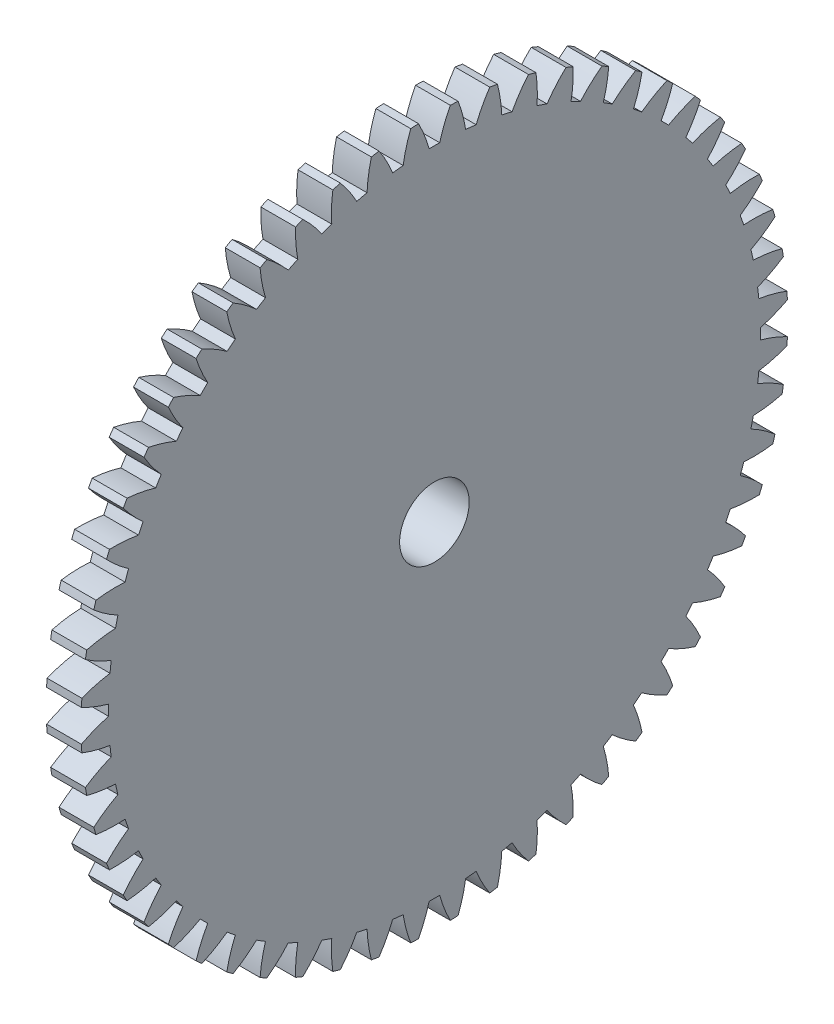
SolidWorks part; units mm, degrees
note: The reader was unsure of these and kept them because the rebuilt part matched: shared geometry of "Sketch1<2>".
ref_plane "Plane1" through (0, 0, 0) normal (0, 0, 1) x (1, 0, 0)
ref_plane "Plane2" through (0, 0, 0) normal (0, 1, 0) x (1, 0, 0)
ref_plane "Plane3" through (0, 0, 0) normal (1, 0, 0) x (0, 0, -1)
sketch "HoldingSke" plane through (0, 0, 0) normal (0, 1, 0) x (1, 0, 0)
  line L0 (0, 0) -> (0.7988, -1.1843)
  line L1 (-15, 0) -> (100, 0) construction
  line L2 (0, 0) -> (-2.1039, 2.3779)
  line L3 (0, 0) -> (-11.863, 4.5341)
  line L4 (0, 0) -> (4.8292, 7.1596)
  line L5 (0, 0) -> (-9.3695, -3.4946)
  line L6 (0, 0) -> (-1.6579, -1.1186)
  line L7 (-2.1039, 2.3779) -> (0.0486, 12.1435)
  line L8 (-76.2, 54.61) -> (-75.5, 54.61)
  line L9 (-71.009, 38.7566) -> (-53.1078, 45.2721)
  line L10 (-76.2, 71.12) -> (104.1128, 71.12)
  line L11 (0, 0) -> (-2, 0)
  line L12 (-76.2, 101.6) -> (-76.173, 101.6)
  line L13 (24.9733, 27.94) -> (52.9518, 28.4284)
  line L14 (24.9733, 27.94) -> (24.9743, 27.94)
  line L15 (24.9733, 27.94) -> (100.4006, 29.5858)
  line L16 (-63.627, -0.7) -> (-12.827, -0.7)
  circle A0 centre (0, 0) radius 2
  circle A1 centre (0, 0) radius 4.5
  circle A2 centre (0, 0) radius 4.5
  circle A3 centre (0, 0) radius 2
  dimension "MHD" = 9
  dimension "Hub_dia" = 9
  dimension "Bore" = 4
  dimension "MBD" = 4
  dimension "Num_teeth" = 56
  dimension "Pitch_radius" = 180.3128
  dimension "Pitch" = 1.4286
  dimension "Width" = 2
  dimension "Overall_len" = 10
  dimension "Show_teeth" = 56
  dimension "Thickness" = 2
  dimension "OAL" = 10.0001
  dimension "T_dim" = 0.7
  dimension "Ap" = 20
  dimension "H" = 19.05
  dimension "Backlash" = 0.027
  dimension "Addendum_fac" = 1
  dimension "Dedendum_fac" = 1.25
  dimension "Clearance_fac" = 0.25
  dimension "Dedendum_add" = 0.001
  dimension "Module" = 0.7
sketch "BasProSke" plane through (0, 0, 0) normal (0, 1, 0) x (1, 0, 0)
  line L0 (-10, 0) -> (60, 0) construction
  line L1 (0, 0) -> (0, 20.3)
  line L2 (0, 0) -> (2, 0)
  line L3 (2, 0) -> (2, 20.3)
  line L4 (2, 20.3) -> (0, 20.3)
  dimension "Diameter" = 40.6
  dimension "Thickness" = 2
revolve "Base-Revolve" add sketch "BasProSke" angle 360 about L0
sketch "TooCutSke" plane through (0, 0, 0) normal (1, 0, 0) x (0, 0, -1)
  line L1 (0, 0) -> (0, 107) construction
  line L2 (0, 0) -> (-0.597, 19.5909) construction
  line L3 (0, 0) -> (-2.1972, 39.1255) construction
  line L4 (-0.597, 19.5909) -> (-1.0986, 19.5627) construction
  arc A0 (0.3036, 18.7215) -> (-0.3036, 18.7215) centre (0, 0) ccw
  arc A1 (0.9277, 20.3042) -> (-0.9277, 20.3042) centre (0, 0) ccw
  circle A2 centre (0, 0) radius 19.6 construction
  circle A3 centre (0, 0) radius 18.418 construction
  arc A4 (-0.3036, 18.7215) -> (-0.9277, 20.3042) centre (-7.866, 16.6538) ccw
  arc A5 (0.9277, 20.3042) -> (0.3036, 18.7215) centre (7.866, 16.6538) ccw
  dimension "Root_dia" = 37.448
  dimension "Overcut_dia" = 40.6508
  dimension "Pitch_dia" = 39.2
  dimension "Base_dia" = 36.836
  dimension "Flank_rad" = 7.84
  dimension "Half_ang" = 3.214
  dimension "Half_CT" = 0.5025
extrude "ToothCut" cut sketch "TooCutSke" along normal through all
fillet "Breaks" [suppressed] radius 0.014
fillet "RootFillets" [suppressed] radius 0.176
pattern_circular "TeethCuts" count 56 every 6.429 about axis through (-10, 0, 0) along (1, 0, 0) of "ToothCut", "RootFillets", "Breaks"
sketch "HubNeaOneSke" plane through (0, 0, 0) normal (-1, 0, 0) x (0, 0, 1)
  circle A0 centre (0, 0) radius 4.5
  dimension "Diameter" = 9
extrude "HubNearOne" add sketch "HubNeaOneSke" along normal blind 8.0001
sketch "HubNeaBotSke" plane through (0, 0, 0) normal (-1, 0, 0) x (0, 0, 1)
  circle A0 centre (0, 0) radius 4.5
  dimension "Diameter" = 9
extrude "HubNearBoth" [suppressed] add sketch "HubNeaBotSke" along normal blind 4
ref_plane "FarPln" through (2, 0, 0) normal (1, 0, 0) x (0, 0, -1)
sketch "HubFarSke" plane through (2, 0, 0) normal (1, 0, 0) x (0, 0, -1)
  circle A0 centre (0, 0) radius 4.5
  dimension "Diameter" = 9
extrude "HubFar" [suppressed] add sketch "HubFarSke" along normal blind 4
sketch "BorSke" plane through (0, 0, 0) normal (1, 0, 0) x (0, 0, -1)
  circle A0 centre (0, 0) radius 2
  dimension "Diameter" = 4
extrude "Bore" cut sketch "BorSke" along normal mid plane 20.0001
sketch "KeySke" plane through (0, 0, 0) normal (1, 0, 0) x (0, 0, -1)
  line L0 (-0.8, 0) -> (-0.8, 2.7)
  line L1 (-0.8, 2.7) -> (0.8, 2.7)
  line L2 (0.8, 2.7) -> (0.8, 0)
  line L3 (0, 0) -> (0, 34) construction
  line L4 (-0.8, 0) -> (0.8, 0)
  dimension "Offset" = 2.7
  dimension "Width" = 1.6
extrude "Keyway" [suppressed] cut sketch "KeySke" along normal mid plane 20.0001
pattern_circular "Keyway2" [suppressed] count 2 every 90 about axis through (-10, 0, 0) along (1, 0, 0)
sketch "Sketch1" plane through (0, 0, 0) normal (0, 0, 1) x (1, 0, 0)
  line L0 (0, 0.3036) -> (0, -0.3036) construction
  circle A0 centre (-4, 0) radius 1.25
  dimension "D1" = 4
curve "Helix/Spiral1" pitch 0.5 height 5 turns 10
extrude "Cut-Extrude1" cut sketch "Sketch1<2>" against normal blind 5
sketch "Sketch1<2>" plane through (0, 0, 0) normal (0, 0, 1) x (1, 0, 0) same geometry as "Sketch1"
sketch "Sketch2" plane through (0, 0, 0) normal (0, 1, 0) x (1, 0, 0)
  line L0 (-5.2214, 3.017) -> (-5.2214, 5.5752) construction
  line L2 (-5.2214, 5.0799) -> (-5.2214, 5.3685)
  line L3 (-5.2214, 5.3685) -> (-5.3964, 5.2675)
  line L4 (-5.3964, 5.1809) -> (-5.2214, 5.0799)
  circle A0 centre (-5.3047, 5.2242) radius 0.0833 construction
  arc A1 (-5.3964, 5.2675) -> (-5.3964, 5.1809) centre (-5.3714, 5.2242) ccw
  spline S0 degree 3 poles (-5.25, 0) (-5.25, 0.0104) (-5.1849, 0.0313) (-4.9069, 0.0625) (-4.4908, 0.0938) (-4, 0.125) (-3.5092, 0.1563) (-3.0931, 0.1875) (-2.8151, 0.2188) (-2.7175, 0.25) (-2.8151, 0.2813) (-3.0931, 0.3125) (-3.5092, 0.3438) (-4, 0.375) (-4.4908, 0.4063) (-4.9069, 0.4375) (-5.1849, 0.4688) (-5.2825, 0.5) (-5.1849, 0.5313) (-4.9069, 0.5625) (-4.4908, 0.5938) (-4, 0.625) (-3.5092, 0.6563) (-3.0931, 0.6875) (-2.8151, 0.7188) (-2.7175, 0.75) (-2.8151, 0.7813) (-3.0931, 0.8125) (-3.5092, 0.8438) (-4, 0.875) (-4.4908, 0.9063) (-4.9069, 0.9375) (-5.1849, 0.9688) (-5.2825, 1) (-5.1849, 1.0313) (-4.9069, 1.0625) (-4.4908, 1.0938) (-4, 1.125) (-3.5092, 1.1563) (-3.0931, 1.1875) (-2.8151, 1.2188) (-2.7175, 1.25) (-2.8151, 1.2813) (-3.0931, 1.3125) (-3.5092, 1.3438) (-4, 1.375) (-4.4908, 1.4063) (-4.9069, 1.4375) (-5.1849, 1.4688) (-5.2825, 1.5) (-5.1849, 1.5313) (-4.9069, 1.5625) (-4.4908, 1.5938) (-4, 1.625) (-3.5092, 1.6563) (-3.0931, 1.6875) (-2.8151, 1.7188) (-2.7175, 1.75) (-2.8151, 1.7813) (-3.0931, 1.8125) (-3.5092, 1.8438) (-4, 1.875) (-4.4908, 1.9063) (-4.9069, 1.9375) (-5.1849, 1.9688) (-5.2825, 2) (-5.1849, 2.0313) (-4.9069, 2.0625) (-4.4908, 2.0938) (-4, 2.125) (-3.5092, 2.1563) (-3.0931, 2.1875) (-2.8151, 2.2188) (-2.7175, 2.25) (-2.8151, 2.2813) (-3.0931, 2.3125) (-3.5092, 2.3438) (-4, 2.375) (-4.4908, 2.4063) (-4.9069, 2.4375) (-5.1849, 2.4688) (-5.2825, 2.5) (-5.1849, 2.5313) (-4.9069, 2.5625) (-4.4908, 2.5938) (-4, 2.625) (-3.5092, 2.6563) (-3.0931, 2.6875) (-2.8151, 2.7188) (-2.7175, 2.75) (-2.8151, 2.7813) (-3.0931, 2.8125) (-3.5092, 2.8438) (-4, 2.875) (-4.4908, 2.9063) (-4.9069, 2.9375) (-5.1849, 2.9688) (-5.2825, 3) (-5.1849, 3.0313) (-4.9069, 3.0625) (-4.4908, 3.0938) (-4, 3.125) (-3.5092, 3.1563) (-3.0931, 3.1875) (-2.8151, 3.2188) (-2.7175, 3.25) (-2.8151, 3.2813) (-3.0931, 3.3125) (-3.5092, 3.3438) (-4, 3.375) (-4.4908, 3.4063) (-4.9069, 3.4375) (-5.1849, 3.4688) (-5.2825, 3.5) (-5.1849, 3.5313) (-4.9069, 3.5625) (-4.4908, 3.5938) (-4, 3.625) (-3.5092, 3.6563) (-3.0931, 3.6875) (-2.8151, 3.7188) (-2.7175, 3.75) (-2.8151, 3.7813) (-3.0931, 3.8125) (-3.5092, 3.8438) (-4, 3.875) (-4.4908, 3.9063) (-4.9069, 3.9375) (-5.1849, 3.9688) (-5.2825, 4) (-5.1849, 4.0313) (-4.9069, 4.0625) (-4.4908, 4.0938) (-4, 4.125) (-3.5092, 4.1563) (-3.0931, 4.1875) (-2.8151, 4.2188) (-2.7175, 4.25) (-2.8151, 4.2813) (-3.0931, 4.3125) (-3.5092, 4.3438) (-4, 4.375) (-4.4908, 4.4063) (-4.9069, 4.4375) (-5.1849, 4.4687) (-5.2825, 4.5) (-5.1849, 4.5312) (-4.9069, 4.5625) (-4.4908, 4.5937) (-4, 4.625) (-3.5092, 4.6562) (-3.0931, 4.6875) (-2.8151, 4.7187) (-2.7175, 4.75) (-2.8151, 4.7812) (-3.0931, 4.8125) (-3.5092, 4.8437) (-4, 4.875) (-4.4908, 4.9062) (-4.9069, 4.9375) (-5.1849, 4.9687) (-5.25, 4.9896) (-5.25, 5) knots 0 0 0 0 0.00625 0.0125 0.01875 0.025 0.03125 0.0375 0.04375 0.05 0.05625 0.0625 0.06875 0.075 0.08125 0.0875 0.09375 0.1 0.10625 0.1125 0.11875 0.125 0.13125 0.1375 0.14375 0.15 0.15625 0.1625 0.16875 0.175 0.18125 0.1875 0.19375 0.2 0.20625 0.2125 0.21875 0.225 0.23125 0.2375 0.24375 0.25 0.25625 0.2625 0.26875 0.275 0.28125 0.2875 0.29375 0.3 0.30625 0.3125 0.31875 0.325 0.33125 0.3375 0.34375 0.35 0.35625 0.3625 0.36875 0.375 0.38125 0.3875 0.39375 0.4 0.40625 0.4125 0.41875 0.425 0.43125 0.4375 0.44375 0.45 0.45625 0.4625 0.46875 0.475 0.48125 0.4875 0.49375 0.5 0.50625 0.5125 0.51875 0.525 0.53125 0.5375 0.54375 0.55 0.55625 0.5625 0.56875 0.575 0.58125 0.5875 0.59375 0.6 0.60625 0.6125 0.61875 0.625 0.63125 0.6375 0.64375 0.65 0.65625 0.6625 0.66875 0.675 0.68125 0.6875 0.69375 0.7 0.70625 0.7125 0.71875 0.725 0.73125 0.7375 0.74375 0.75 0.75625 0.7625 0.76875 0.775 0.78125 0.7875 0.79375 0.8 0.80625 0.8125 0.81875 0.825 0.83125 0.8375 0.84375 0.85 0.85625 0.8625 0.86875 0.875 0.88125 0.8875 0.89375 0.9 0.90625 0.9125 0.91875 0.925 0.93125 0.9375 0.94375 0.95 0.95625 0.9625 0.96875 0.975 0.98125 0.9875 0.99375 1 1 1 1 construction
  point P11 (-5.4714, 5.2242)
  dimension "D2" = 0.05
  dimension "D1" = 0.25
sweep "Cut-Sweep1" cut profiles "Sketch2" path "Helix/Spiral1"
ref_plane "Plane4" through (0, 0, -4.5) normal (0, 0, 1) x (1, 0, 0)
sketch "Sketch3" plane through (0, 0, -4.5) normal (0, 0, 1) x (1, 0, 0)
  circle A0 centre (-4, 0) radius 1.55
extrude "Cut-Extrude2" cut sketch "Sketch3" along normal blind 5 draft 45
equation "' \"Module@HoldingSke\" = 6.35"
equation "' \"Num_teeth@HoldingSke\" = 12"
equation "' \"Ap@HoldingSke\" =  20"
equation "' \"Width@HoldingSke\" = 0.5 * 25.4"
equation "' \"Hub_dia@HoldingSke\"= 1 * 25.4"
equation "' \"Overall_len@HoldingSke\" = 1.0 * 25.4"
equation "' \"Bore@HoldingSke\" = 0.75 * 25.4"
equation "' \"T_dim@HoldingSke\" = 0.1 * 25.4"
equation "' \"Width@KeySke\" = 0.25 * 25.4"
equation "' \"Show_teeth@HoldingSke\" = 13"
equation "' \"Backlash@HoldingSke\" = 0.009 * 25.4"
equation "' \"Addendum_fac@HoldingSke\" = 1.0"
equation "' \"Dedendum_fac@HoldingSke\" = 1.25"
equation "' \"Dedendum_add@HoldingSke\" = 0.00005 * 25.4"
equation "' \"Clearance_fac@HoldingSke\" = 0.25"
equation "\"Pitch@HoldingSke\" = 1 / \"Module@HoldingSke\""
equation "\"Overcut_dia@TooCutSke\" = (\"Num_teeth@HoldingSke\" + 2 * \"Addendum_fac@HoldingSke\") / \"Pitch@HoldingSke\" + 0.002 * 25.4"
equation "\"Pitch_dia@TooCutSke\" = \"Num_teeth@HoldingSke\" / \"Pitch@HoldingSke\""
equation "\"Base_dia@TooCutSke\" = \"Num_teeth@HoldingSke\" / \"Pitch@HoldingSke\" * cos((\"Ap@HoldingSke\"  * 3.14159265 / 180))"
equation "\"Root_dia@TooCutSke\" = (\"Num_teeth@HoldingSke\" + 2) / \"Pitch@HoldingSke\" - 2 * (\"Addendum_fac@HoldingSke\" + \"Dedendum_fac@HoldingSke\") / \"Pitch@HoldingSke\" - \"Dedendum_add@HoldingSke\" * 2"
equation "\"Half_ang@TooCutSke\" = 180 / \"Num_teeth@HoldingSke\""
equation "\"Half_CT@TooCutSke\" = \"Num_teeth@HoldingSke\" / \"Pitch@HoldingSke\" * sin((3.14159265 / 2 / \"Num_teeth@HoldingSke\")) / 2 - 7 * \"Backlash@HoldingSke\" / 4"
equation "\"Flank_rad@TooCutSke\" = \"Num_teeth@HoldingSke\" / \"Pitch@HoldingSke\" / 5"
equation "\"Radius@RootFillets\" = \"Clearance_fac@HoldingSke\" / \"Pitch@HoldingSke\" + \"Dedendum_add@HoldingSke\""
equation "\"Break_rad@Breaks\" = 0.02 / \"Pitch@HoldingSke\""
equation "\"Thickness@HoldingSke\" = \"Width@HoldingSke\""
equation "\"OAL@HoldingSke\" = \"Thickness@HoldingSke\""
equation "\"MHD@HoldingSke\" = (\"Num_teeth@HoldingSke\" + 2) / \"Pitch@HoldingSke\" - 2 * (\"Addendum_fac@HoldingSke\" + \"Dedendum_fac@HoldingSke\")  / \"Pitch@HoldingSke\" - \"Dedendum_add@HoldingSke\" * 2"
equation "\"MBD@HoldingSke\" = (\"Num_teeth@HoldingSke\" + 2) / \"Pitch@HoldingSke\" - 2 * (\"Addendum_fac@HoldingSke\" + \"Dedendum_fac@HoldingSke\")  / \"Pitch@HoldingSke\" - \"Dedendum_add@HoldingSke\" * 2 - 0.002 * 25.4"
equation "\"MHD@HoldingSke\" = ((sgn( \"MHD@HoldingSke\" - \"Hub_dia@HoldingSke\" )-1)*( \"MHD@HoldingSke\" - \"Hub_dia@HoldingSke\" ))/-2+ \"Hub_dia@HoldingSke\""
equation "\"MBD@HoldingSke\" = ((sgn( \"MBD@HoldingSke\" - \"Bore@HoldingSke\" )-1)*( \"MBD@HoldingSke\" - \"Bore@HoldingSke\" ))/-2+ \"Bore@HoldingSke\""
equation "\"OAL@HoldingSke\" = ((sgn( \"OAL@HoldingSke\" - \"Overall_len@HoldingSke\" )+1)*( \"OAL@HoldingSke\" - \"Overall_len@HoldingSke\" ))/2 + \"Overall_len@HoldingSke\" + 0.000002 * 25.4"
equation "\"Num_teeth@TeethCuts\" = int( \"Show_teeth@HoldingSke\" ) + 1"
equation "\"Num_teeth@TeethCuts\" = ((sgn( \"Num_teeth@TeethCuts\" - \"Num_teeth@HoldingSke\" )-1)*( \"Num_teeth@TeethCuts\" - \"Num_teeth@HoldingSke\" ))/-2+ \"Num_teeth@HoldingSke\""
equation "\"Num_teeth@TeethCuts\" = ((sgn( \"Num_teeth@TeethCuts\" - 2.0)+1)*( \"Num_teeth@TeethCuts\" - 2.0))/2 +2.0"
equation "\"Angle@TeethCuts\" = 360.0 / \"Num_teeth@HoldingSke\""
equation "\"Diameter@BasProSke\" = (\"Num_teeth@HoldingSke\" + 2 * \"Addendum_fac@HoldingSke\") / \"Pitch@HoldingSke\""
equation "\"Thickness@BasProSke\"  = \"Thickness@HoldingSke\""
equation "' \"Fillet_rad@BasProSke\" =  \"Thickness@HoldingSke\" * 0.05"
equation "\"MHD@HoldingSke\" = ((sgn( \"MHD@HoldingSke\" - \"Root_dia@TooCutSke\" )-1)*( \"MHD@HoldingSke\" - \"Root_dia@TooCutSke\" ))/-2+ \"Root_dia@TooCutSke\""
equation "\"Diameter@HubNeaOneSke\" = \"MHD@HoldingSke\""
equation "\"Length@HubNearOne\" = \"OAL@HoldingSke\" - \"Thickness@BasProSke\""
equation "\"Diameter@HubNeaBotSke\" = \"MHD@HoldingSke\""
equation "\"Length@HubNearBoth\" = ( \"OAL@HoldingSke\" - \"Thickness@BasProSke\" ) / 2.0"
equation "\"Thickness@FarPln\" = \"Thickness@BasProSke\""
equation "\"Diameter@HubFarSke\" = \"MHD@HoldingSke\""
equation "\"Length@HubFar\" = ( \"OAL@HoldingSke\" - \"Thickness@BasProSke\" ) / 2.0"
equation "\"Diameter@BorSke\" = \"MBD@HoldingSke\""
equation "\"D1@Bore\" = \"OAL@HoldingSke\" * 2.0"
equation "\"D1@Keyway\" = \"OAL@HoldingSke\" * 2.0"
equation "\"Offset@KeySke\" = \"T_dim@HoldingSke\" + \"MBD@HoldingSke\" / 2.0"
